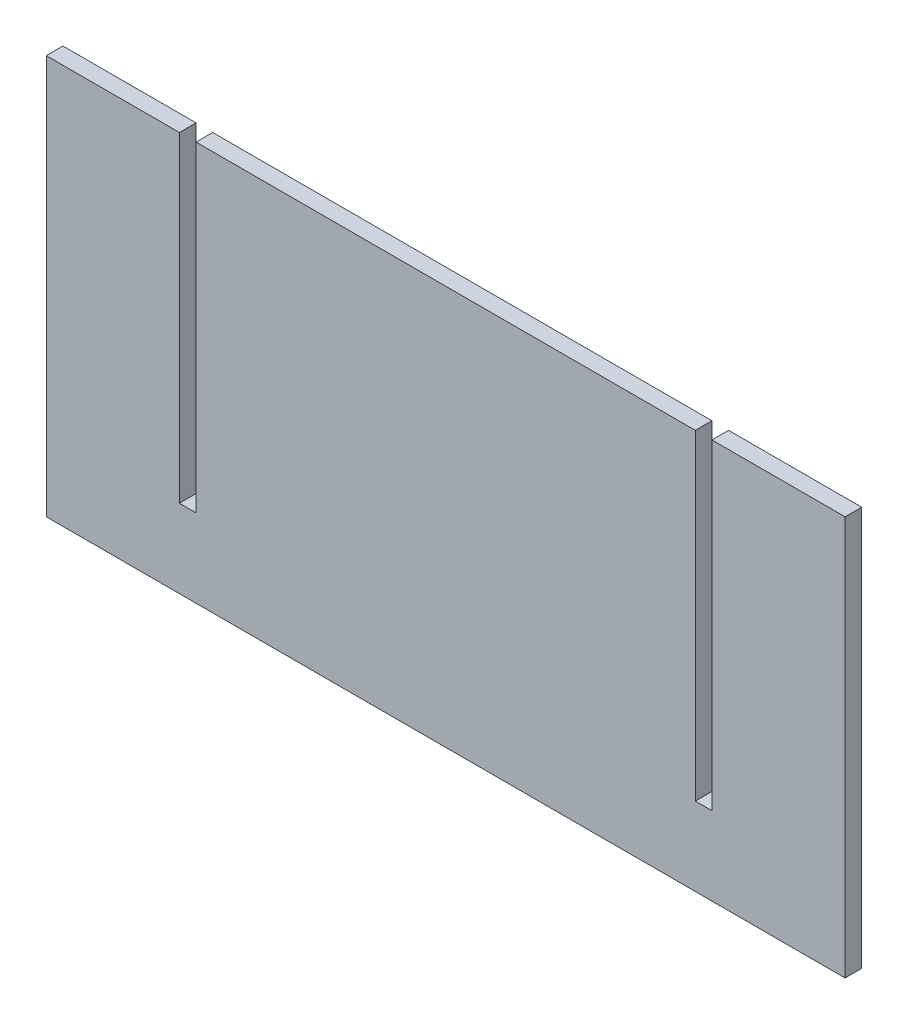
SolidWorks part; units mm, degrees
ref_plane "Front Plane" through (0, 0, 0) normal (0, 0, 1) x (1, 0, 0)
ref_plane "Top Plane" through (0, 0, 0) normal (0, 1, 0) x (1, 0, 0)
ref_plane "Right Plane" through (0, 0, 0) normal (1, 0, 0) x (0, 0, -1)
sketch "Sketch1" plane through (0, 0, 0) normal (0, 0, 1) x (1, 0, 0)
  line L0 (76.2, 76.2) -> (76.2, 0) construction
  line L1 (0, 0) -> (152.4, 0)
  line L2 (0, 0) -> (0, 76.2)
  line L3 (0, 76.2) -> (152.4, 76.2)
  line L4 (152.4, 0) -> (152.4, 76.2)
  line L5 (25.4, 76.2) -> (28.575, 76.2)
  line L6 (25.4, 76.2) -> (25.4, 14.9428)
  line L7 (25.4, 14.9428) -> (28.575, 14.9428)
  line L8 (28.575, 76.2) -> (28.575, 14.9428)
  line L9 (127, 14.9428) -> (123.825, 14.9428)
  line L10 (123.825, 76.2) -> (123.825, 14.9428)
  line L11 (127, 76.2) -> (127, 14.9428)
  dimension "D1" = 152.4
  dimension "D2" = 76.2
  dimension "D3" = 25.4
  dimension "D4" = 3.175
extrude "Boss-Extrude1" add sketch "Sketch1" along normal blind 3.175 contours L0 L3 L8 L7 L6 L2 L1 | L3 L0 L1 L4 L11 L9 L10 region at (113.9149, 37.8411, 0) region at (38.4851, 37.8411, 0)
